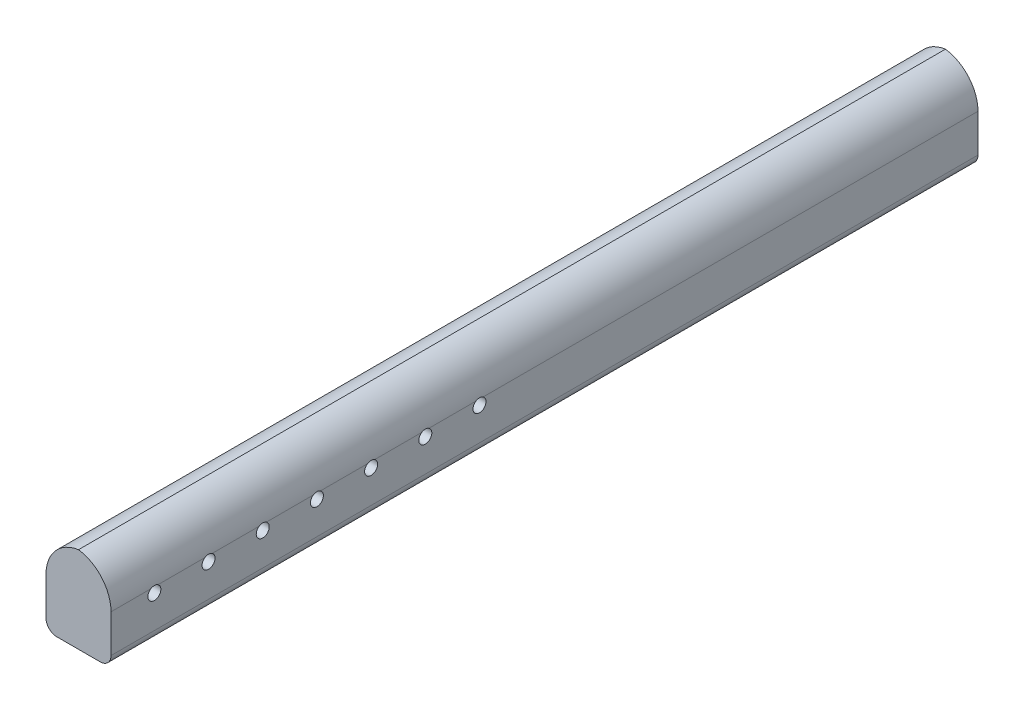
SolidWorks part; units mm, degrees
ref_plane "Plan de face" through (0, 0, 0) normal (0, 0, 1) x (1, 0, 0)
ref_plane "Plan de dessus" through (0, 0, 0) normal (0, 1, 0) x (1, 0, 0)
ref_plane "Plan de droite" through (0, 0, 0) normal (1, 0, 0) x (0, 0, -1)
sketch "Esquisse1" plane through (0, 0, 0) normal (0, 0, 1) x (1, 0, 0)
  line L1 (3, 4) -> (-3, 4)
  line L2 (3, 4) -> (3, -4)
  line L3 (3, -4) -> (-3, -4)
  line L4 (-3, 4) -> (-3, -4)
  line L5 (3, 4) -> (-3, -4) construction
  line L6 (3, -4) -> (-3, 4) construction
  point P0 (0, 0)
  dimension "D1" = 6
  dimension "D2" = 8
extrude "Boss.-Extru.1" add sketch "Esquisse1" along normal blind 80
fillet "Congé1" radius 3.5 2 edges at (-3, 4, 40) (3, 4, 40)
fillet "Congé2" radius 1 2 edges at (3, -4, 40) (-3, -4, 40)
sketch "Esquisse2" plane through (-3, 0, 0) normal (-1, 0, 0) x (0, 0, 1)
  line L0 (0, 0) -> (80, 0) construction
  line L1 (80, 0.5) -> (80, -3) construction
  circle A0 centre (46, 0) radius 0.6
  circle A1 centre (51, 0) radius 0.6
  circle A2 centre (56, 0) radius 0.6
  circle A3 centre (61, 0) radius 0.6
  circle A4 centre (66, 0) radius 0.6
  circle A5 centre (71, 0) radius 0.6
  circle A6 centre (76, 0) radius 0.6
  dimension "D1" = 1.2
  dimension "D2" = 46
  dimension "D3" = 7
extrude "Enlèv. mat.-Extru.1" cut sketch "Esquisse2" against normal through all
